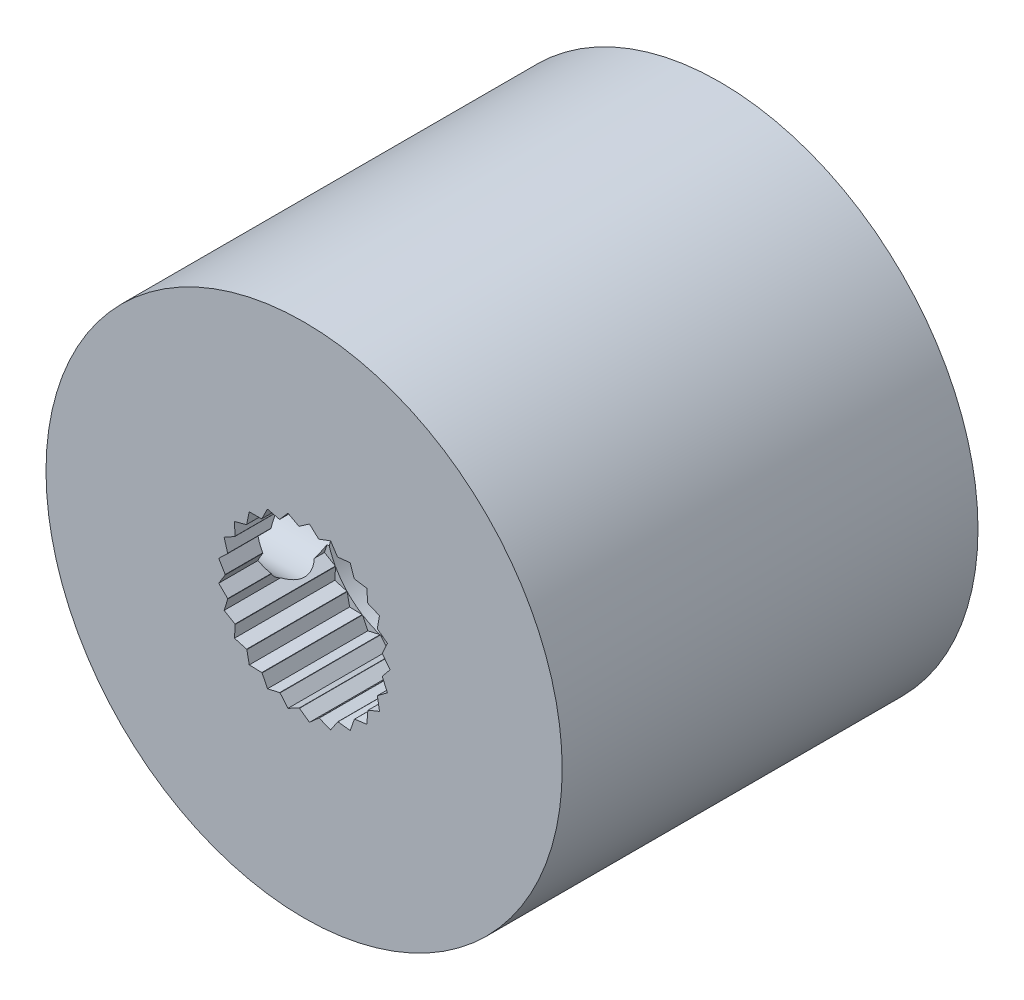
SolidWorks part; units mm, degrees
material "1060 Alloy"
ref_plane "Front Plane" through (0, 0, 0) normal (0, 0, 1) x (1, 0, 0)
ref_plane "Top Plane" through (0, 0, 0) normal (0, 1, 0) x (1, 0, 0)
ref_plane "Right Plane" through (0, 0, 0) normal (1, 0, 0) x (0, 0, -1)
sketch "Sketch1" plane through (0, 0, 0) normal (0, 0, 1) x (1, 0, 0)
  circle A0 centre (0, 0) radius 10
extrude "Boss-Extrude1" add sketch "Sketch1" along normal blind 2
sketch "Sketch2" plane through (0, 0, 2) normal (0, 0, 1) x (1, 0, 0)
  circle A0 centre (0, 0) radius 4.5
extrude "Boss-Extrude2" add sketch "Sketch2" along normal blind 2.5
sketch "Sketch3" plane through (0, 0, 4.5) normal (0, 0, 1) x (1, 0, 0)
  circle A0 centre (0, 0) radius 2.75
extrude "Cut-Extrude1" cut sketch "Sketch3" against normal blind 5
sketch "Sketch4" plane through (0, 0, 0) normal (0, 0, 1) x (1, 0, 0)
  circle A0 centre (0, 0) radius 1.5
extrude "Cut-Extrude2" [suppressed] cut sketch "Sketch4" against normal through all
sketch "Sketch5" plane through (0, 0, 4.5) normal (0, 0, 1) x (1, 0, 0)
  line L1 (-2.6565, 0.6821) -> (-2.6823, 0.6062)
  line L3 (-2.75, 0) -> (-2.9763, 0.376)
  line L4 (-2.9763, 0.376) -> (-2.6565, 0.6821)
  line L5 (-2.6823, 0.6062) -> (-2.75, 0)
  circle A2 centre (0, 0) radius 2.75 construction
extrude "Cut-Extrude3" cut sketch "Sketch5" against normal blind 3.5 contours L5 L3 L4 L1
pattern_circular "CirPattern1" count 25 over 360 about axis through (0, 0, -0.5) along (0, 0, 1) of "Cut-Extrude3"
sketch "Sketch6" plane through (0, 0, 2) normal (0, 0, 1) x (1, 0, 0)
  line L0 (0, 10) -> (0, -10) construction
  line L1 (0, -10) -> (10, 0) construction
  line L2 (10, 0) -> (-10, 0) construction
  line L3 (0, 0) -> (-7.0711, 7.0711) construction
  circle A0 centre (0, 0) radius 10 construction
  circle A1 centre (-7, 0) radius 1.5
  circle A2 centre (7, 0) radius 1.5
  circle A3 centre (0, 7) radius 1.5
  circle A4 centre (0, -7) radius 1.5
  dimension "D1" = 3
extrude "Cut-Extrude4" cut sketch "Sketch6" against normal through all
fillet "Fillet1" radius 0.1 1 edges at (5.5, 0, 2)
thread "Thread1" pitch 0.3175 method extrude profile "Thread Profile3" start angle 0, offset 0, length 2, pitch 0.3175, diameter 3
ref_plane "Plane3" through (5.5, 0, 1.9) normal (0, -1, 0) x (-1, 0, 0)
sketch "Thread Profile3" plane through (5.5, 0, 1.9) normal (0, -1, 0) x (-1, 0, 0)
  line L0 (0, 0) -> (0, 0.3175) construction
  line L11 (0, 0) -> (0, 0.2778)
  line L12 (0, 0.2778) -> (-0.1719, 0.1786)
  line L13 (-0.1719, 0.1786) -> (-0.1719, 0.0992)
  line L15 (-0.1719, 0.0992) -> (0, 0)
  line L17 (-0.1719, 0.1389) -> (0, 0.1389) construction
  point P2 (0, 0)
  dimension "Pitch" = 0.3175
  dimension "Profile_Angle" = 60
  dimension "Profile_Land" = 0.0794
  dimension "Profile_Height" = 0.1719
sketch "Sketch7" plane through (0, 0, 4.5) normal (0, 0, 1) x (1, 0, 0)
  circle A0 centre (0, 0) radius 4.5
  circle A1 centre (0, 0) radius 11.5681
extrude "Cut-Extrude5" cut sketch "Sketch7" against normal blind 10
sketch "Sketch8" plane through (0, 0, 0) normal (0, 0, -1) x (-1, 0, 0)
  circle A0 centre (0, 0) radius 4.5
extrude "Boss-Extrude3" add sketch "Sketch8" along normal blind 10
sketch "Sketch9" plane through (0, 0, -10) normal (0, 0, -1) x (-1, 0, 0)
  line L0 (0, 0) -> (0, 4.7011) construction
  line L2 (0, 5.7735) -> (-5, 2.8868)
  line L3 (-5, 2.8868) -> (-5, -2.8868)
  line L4 (-5, -2.8868) -> (0, -5.7735)
  line L5 (0, -5.7735) -> (5, -2.8868)
  line L6 (5, -2.8868) -> (5, 2.8868)
  line L7 (5, 2.8868) -> (0, 5.7735)
  circle A0 centre (0, 0) radius 5 construction
  circle A1 centre (0, 0) radius 9
  circle M7 centre (0, 0) radius 4.5
  dimension "D2" = 18
  dimension "D1" = 10
extrude "Boss-Extrude4" add sketch "Sketch9" against normal up to surface (14.5 mm away) contours L6 L7 L2 L3 L4 L5 M7 | A1 L7 L6 L5 L4 L3 L2 region at (-2.4236, 4.1978, -10) region at (8.7454, 0, -10) up to face at (4.5, 0, 4.5)
sketch "Sketch10" plane through (0, 0, -10) normal (0, 0, -1) x (-1, 0, 0)
  line L0 (0, 0) -> (0, 5.8351) construction
  line L2 (0, 7.5056) -> (-6.5, 3.7528)
  line L3 (-6.5, 3.7528) -> (-6.5, -3.7528)
  line L4 (-6.5, -3.7528) -> (0, -7.5056)
  line L5 (0, -7.5056) -> (6.5, -3.7528)
  line L6 (6.5, -3.7528) -> (6.5, 3.7528)
  line L7 (6.5, 3.7528) -> (0, 7.5056)
  circle A0 centre (0, 0) radius 6.5 construction
  dimension "D1" = 13
extrude "Cut-Extrude6" cut sketch "Sketch10" against normal blind 6
sketch "Sketch11" plane through (0, 0, 0) normal (1, 0, 0) x (0, 0, -1)
  line L0 (-4.9409, 0) -> (12.2122, 0) construction
  line L1 (10, -9) -> (10, 9) construction
  circle A0 centre (-1.9409, 0) radius 1.25
  circle A1 centre (7, 0) radius 1.25
  dimension "D1" = 2.5
  dimension "D3" = 2.5
  dimension "D2" = 3
  dimension "D4" = 3
extrude "Cut-Extrude7" cut sketch "Sketch11" against normal blind 9
